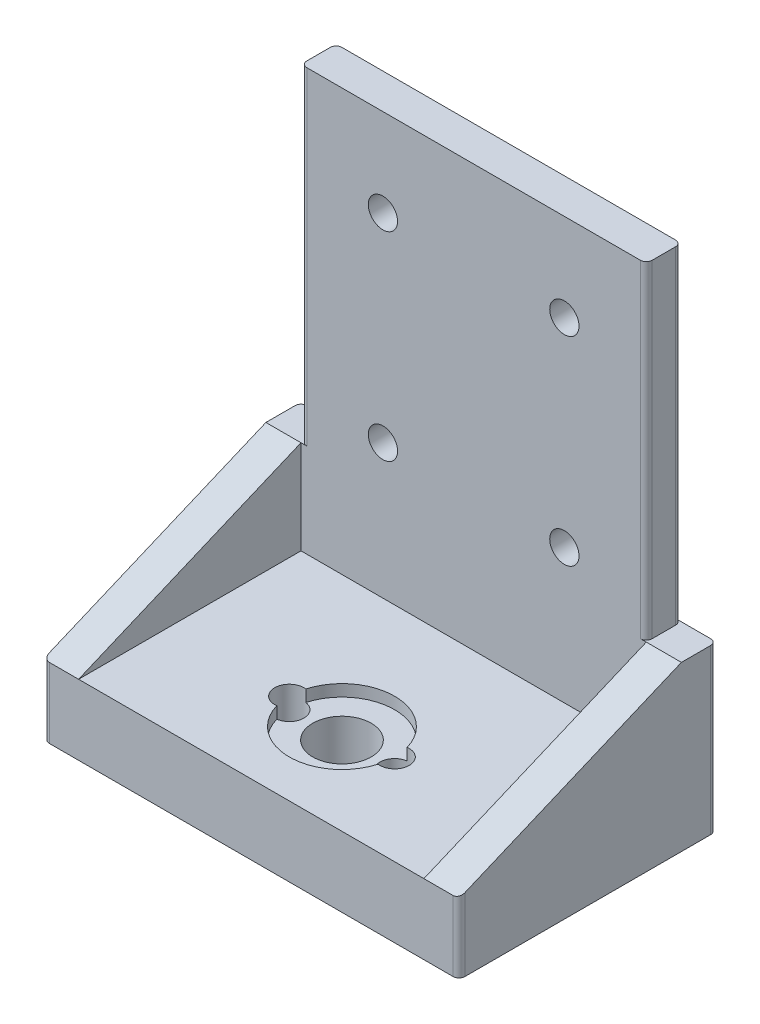
SolidWorks part; units mm, degrees
ref_plane "Front Plane" through (0, 0, 0) normal (0, 0, 1) x (1, 0, 0)
ref_plane "Top Plane" through (0, 0, 0) normal (0, 1, 0) x (1, 0, 0)
ref_plane "Right Plane" through (0, 0, 0) normal (1, 0, 0) x (0, 0, -1)
sketch "Sketch1" plane through (0, 0, 0) normal (0, 1, 0) x (1, 0, 0)
  line L1 (0, 0) -> (35.5, 0)
  line L2 (0, 0) -> (0, 22)
  line L3 (0, 22) -> (35.5, 22)
  line L4 (35.5, 0) -> (35.5, 22)
  dimension "D1" = 35.5
  dimension "D2" = 22
extrude "Boss-Extrude1" add sketch "Sketch1" along normal blind 42
sketch "Sketch2" plane through (35.5, 0, 0) normal (1, 0, 0) x (0, 0, -1)
  line L1 (0, 42) -> (0, 0) construction
  line L2 (0, 6) -> (19, 14)
  line L3 (0, 42) -> (0, 6)
  line L4 (19, 14) -> (19, 42)
  line L5 (0, 42) -> (22, 42) construction
  line L6 (19, 42) -> (0, 42)
  point P0 (0, 0)
extrude "Cut-Extrude1" cut sketch "Sketch2" against normal through all
sketch "Sketch3" plane through (0, 42, 0) normal (0, 1, 0) x (1, 0, 0)
  line L0 (0, 19) -> (35.5, 19) construction
  line L1 (0, 22) -> (3, 22)
  line L2 (0, 22) -> (0, 19)
  line L3 (0, 19) -> (3, 19)
  line L4 (3, 22) -> (3, 19)
  line L6 (35.5, 22) -> (32.5, 22)
  line L7 (35.5, 22) -> (35.5, 19)
  line L8 (35.5, 19) -> (32.5, 19)
  line L9 (32.5, 22) -> (32.5, 19)
extrude "Cut-Extrude2" cut sketch "Sketch3" against normal blind 28
sketch "Sketch4" plane through (0, 0, 0) normal (0, 0, 1) x (1, 0, 0)
  line L0 (0, 6) -> (35.5, 6) construction
  line L1 (3, 6) -> (32.5, 6)
  line L2 (3, 6) -> (3, 16)
  line L3 (3, 16) -> (32.5, 16)
  line L4 (32.5, 6) -> (32.5, 16)
extrude "Cut-Extrude3" cut sketch "Sketch4" against normal blind 19
hole_wizard "Hole1" positions "Sketch5" profile "Sketch6" legacy end condition through all
sketch "Sketch5" plane through (0, 0, 0) normal (0, -1, 0) x (-1, 0, 0)
  point P0 (-17.75, 7.75)
sketch "Sketch6" plane through (17.75, 0, -7.75) normal (1, 0, 0) x (0, 0, -1)
  line L0 (0, 0) -> (0, 42)
  line L1 (0, 42) -> (4.5, 42)
  line L2 (4.5, 42) -> (4.5, 5)
  line L3 (4.5, 5) -> (2.5, 5)
  line L4 (2.5, 5) -> (2.5, 0)
  line L5 (2.5, 0) -> (0, 0)
  line L6 (0, 110) -> (0, -10) construction
  dimension "Diameter" = 9
  dimension "Depth" = 42
  dimension "C-Bore Diameter" = 5
  dimension "C-Bore Depth" = 5
hole_wizard "Ø2.5mm Dowel Hole1" positions "Sketch7" profile "Sketch8" hole size "Ø2.5" standard "JIS" end condition through all
sketch "Sketch7" plane through (0, 0, 0) normal (0, -1, 0) x (-1, 0, 0)
  point P0 (-22.25, 7.75)
  point P2 (-13.25, 7.75)
sketch "Sketch8" plane through (22.25, 0, -7.75) normal (1, 0, 0) x (0, 0, -1)
  line L0 (0, 0) -> (0, 42)
  line L1 (0, 42) -> (1.25, 42)
  line L2 (1.25, 42) -> (1.25, 0)
  line L5 (1.25, 0) -> (0, 0)
  line L11 (0, -6.35) -> (0, 107.95) construction
  dimension "Thru Hole Dia." = 2.5
  dimension "Thru Hole Depth" = 42
hole_wizard "Ø2.5mm Dowel Hole2" positions "Sketch9" profile "Sketch10" hole size "Ø2.5" standard "JIS" end condition through all
sketch "Sketch9" plane through (0, 0, -22) normal (0, 0, -1) x (-1, 0, 0)
  point P0 (-10, 17.5)
  point P2 (-25.5, 17.5)
  point P4 (-25.5, 34.5)
  point P6 (-10, 34.5)
  point P15 (0, 0)
  point P16 (0, 0)
  point P17 (0, 0)
  point P18 (0, 0)
sketch "Sketch10" plane through (10, 17.5, -22) normal (1, 0, 0) x (0, 1, 0)
  line L0 (0, 0) -> (0, 22)
  line L1 (0, 22) -> (1.25, 22)
  line L2 (1.25, 22) -> (1.25, 0)
  line L5 (1.25, 0) -> (0, 0)
  line L11 (0, -6.35) -> (0, 107.95) construction
  dimension "Thru Hole Dia." = 2.5
  dimension "Thru Hole Depth" = 22
fillet "Fillet1" radius 0.5 8 edges at (0, 7, -22) (35.5, 7, -22) (0, 3, 0) (35.5, 3, 0) (3, 28, -22) (32.5, 28, -22) (32.5, 28, -19) (3, 28, -19)
